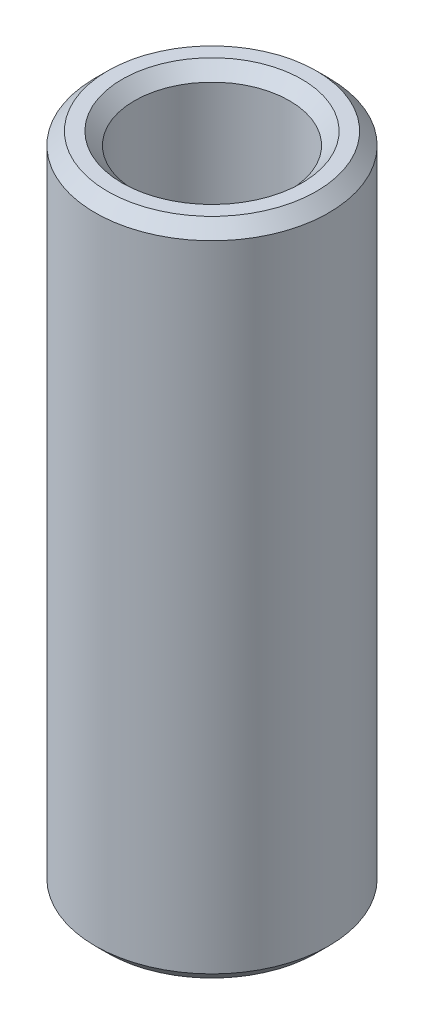
SolidWorks part; units mm, degrees
ref_plane "Front Plane" through (0, 0, 0) normal (0, 0, 1) x (1, 0, 0)
ref_plane "Top Plane" through (0, 0, 0) normal (0, 1, 0) x (1, 0, 0)
ref_plane "Right Plane" through (0, 0, 0) normal (1, 0, 0) x (0, 0, -1)
sketch "Sketch1" plane through (0, 0, 0) normal (0, 1, 0) x (1, 0, 0)
  circle A0 centre (0, 0) radius 27.5
  dimension "SLEEVE_OD" = 55
extrude "Boss-Extrude1" add sketch "Sketch1" along normal blind 155.3418
sketch "Sketch2" plane through (0, 0, 0) normal (0, 1, 0) x (1, 0, 0)
  circle A0 centre (0, 0) radius 18.2516
  dimension "BORE_D" = 36.5032
extrude "Cut-Extrude1" cut sketch "Sketch2" along normal through all
chamfer "Chamfer1" distance 2.9157 angle 45 4 edges at (0, 155.3418, 18.2516) (0, 0, 18.2516) (0, 0, 27.5) (0, 155.3418, 27.5)
